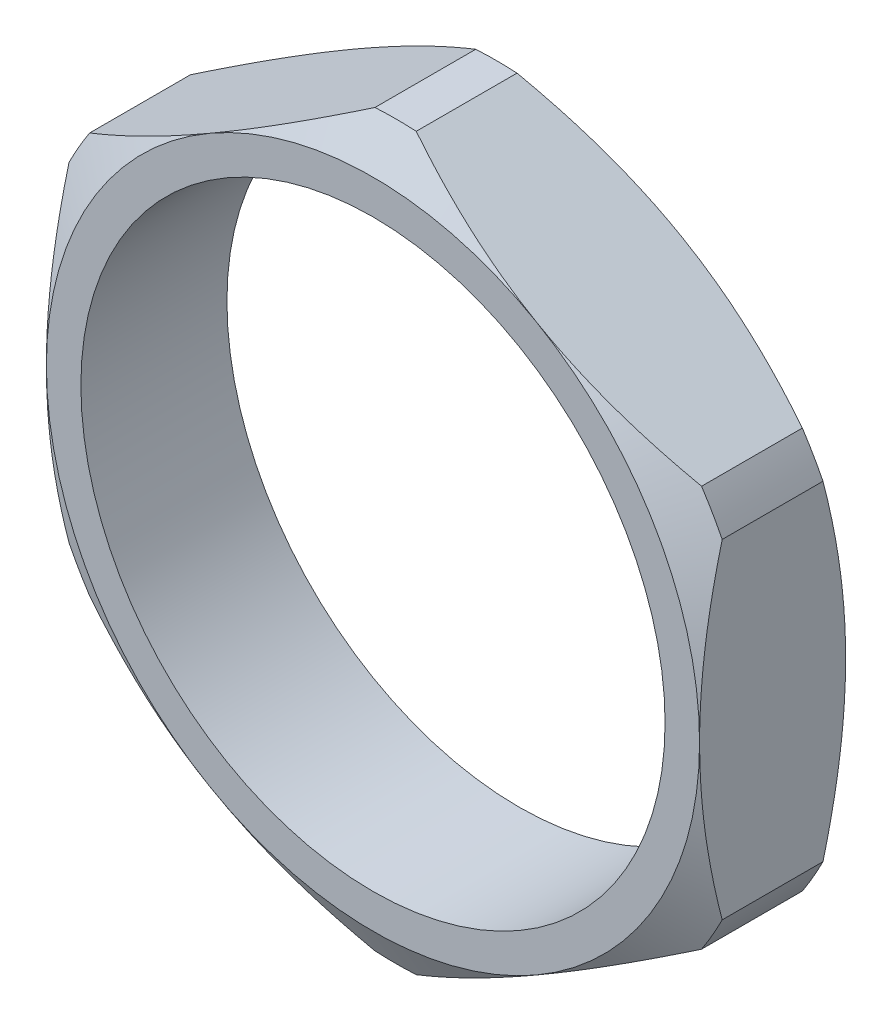
SolidWorks part; units mm, degrees
material "Lead Free Brass, UNS C69300"
ref_plane "Front Plane" through (0, 0, 0) normal (0, 0, 1) x (1, 0, 0)
ref_plane "Top Plane" through (0, 0, 0) normal (0, 1, 0) x (1, 0, 0)
ref_plane "Right Plane" through (0, 0, 0) normal (1, 0, 0) x (0, 0, -1)
sketch "Sketch1" plane through (0, 0, 0) normal (1, 0, 0) x (0, 0, -1)
  line L0 (-1.5875, 0) -> (1.5875, 0) construction
  line L5 (0, 7.1) -> (0, -7.1) construction
  point P5 (0, 6.35)
  point P6 (0, -6.35)
  point P7 (-0.6804, 0)
  dimension "Height" = 3.175
  dimension "Width" = 14.2
  dimension "Thread Size Decimal Equivalent" = 12.7
  dimension "Thread Pitch" = 0.9071
sketch "Sketch2" plane through (0, 0, 0) normal (1, 0, 0) x (0, 0, -1)
  line L0 (-1.5875, 7.1) -> (-1.0956, 7.952)
  line L1 (-1.5875, 7.1) -> (1.5875, 7.1)
  line L2 (-1.5875, 7.1) -> (-1.5875, 6.35)
  line L3 (-1.5875, 6.35) -> (1.5875, 6.35)
  line L4 (1.5875, 7.1) -> (1.5875, 6.35)
  line L5 (-1.0956, 7.952) -> (1.0956, 7.952)
  line L6 (1.0956, 7.952) -> (1.5875, 7.1)
  line L7 (-1.5875, 0) -> (1.5875, 0) construction
  line L8 (-1.5875, 0) -> (1.5875, 0) construction
  line L9 (-2.4379, 6.4482) -> (-1.9844, 5.6626) construction
  line L10 (-1.9844, 5.6626) -> (-1.5308, 6.4482) construction
  line L11 (-1.5308, 6.4482) -> (-2.4379, 6.4482) construction
  line L12 (-2.3812, 6.35) -> (-1.5875, 6.35) construction
  line L13 (-1.9844, 6.4482) -> (-1.9844, 6.35) construction
  line L14 (-1.9844, 6.35) -> (-1.9844, 5.7608) construction
  line L15 (-1.9844, 5.7608) -> (-1.9844, 5.6626) construction
  line L16 (-2.0411, 5.7608) -> (-1.9277, 5.7608)
  line L17 (-2.4096, 6.3991) -> (-1.5592, 6.3991)
  line L18 (-1.9277, 5.7608) -> (-1.5592, 6.3991)
  line L19 (-2.0411, 5.7608) -> (-2.4096, 6.3991)
  point P25 (-1.9844, 6.3991)
  dimension "D1" = 15.904
  dimension "D2" = 60
  dimension "D3" = 0.9071
  dimension "D4" = 0.1134
sketch "Drawing Ref" plane through (0, 0, 0) normal (0, 0, 1) x (1, 0, 0)
  line L0 (0, 0) -> (0, -6.4482) construction
  line L1 (0, 0) -> (4.5596, -4.5596) construction
  circle A0 centre (0, 0) radius 6.4482 construction
  dimension "D1" = 45
sketch "Sketch3" plane through (0, 0, 0) normal (1, 0, 0) x (0, 0, -1)
  line L0 (-1.5875, 7.1) -> (-1.0956, 7.952) construction
  line L1 (-1.0956, 7.952) -> (1.0956, 7.952) construction
  line L2 (1.0956, 7.952) -> (1.5875, 7.1) construction
  line L3 (1.5875, 7.1) -> (1.5875, 6.35) construction
  line L4 (-1.5875, 6.35) -> (1.5875, 6.35) construction
  line L5 (-1.5875, 7.1) -> (-1.5875, 6.35) construction
  line L6 (-1.5875, 7.1) -> (-1.0956, 7.952)
  line L7 (-1.0956, 7.952) -> (1.0956, 7.952)
  line L8 (1.0956, 7.952) -> (1.5875, 7.1)
  line L9 (1.5875, 7.1) -> (1.5875, 6.35)
  line L10 (-1.5875, 6.35) -> (1.5875, 6.35)
  line L11 (-1.5875, 7.1) -> (-1.5875, 6.35)
revolve "Revolve1" add sketch "Sketch3" angle 360 about L0
sketch "Sketch4" plane through (0, 0, 0) normal (0, 0, 1) x (1, 0, 0)
  line L1 (0, 8.1984) -> (-7.1, 4.0992)
  line L2 (-7.1, 4.0992) -> (-7.1, -4.0992)
  line L3 (-7.1, -4.0992) -> (0, -8.1984)
  line L4 (0, -8.1984) -> (7.1, -4.0992)
  line L5 (7.1, -4.0992) -> (7.1, 4.0992)
  line L6 (7.1, 4.0992) -> (0, 8.1984)
  circle A0 centre (0, 0) radius 7.1 construction
extrude "Cut-Extrude1" cut sketch "Sketch4" against normal through all both and the other way through all flip side to cut
sketch "Sketch5" [suppressed] plane through (0, 0, 1.5875) normal (0, 0, 1) x (1, 0, 0)
  circle A0 centre (0, 0) radius 6.35
curve "Helix/Spiral1" [suppressed] pitch 0.9071 height 4.0821 turns 4.5
sketch "Sketch6" [suppressed] plane through (0, 0, 0) normal (1, 0, 0) x (0, 0, -1)
  line L0 (-2.0411, 5.7608) -> (-1.9277, 5.7608) construction
  line L1 (-2.0411, 5.7608) -> (-2.4096, 6.3991) construction
  line L2 (-2.4096, 6.3991) -> (-1.5592, 6.3991) construction
  line L3 (-1.9277, 5.7608) -> (-1.5592, 6.3991) construction
  line L4 (-2.0411, 5.7608) -> (-1.9277, 5.7608)
  line L5 (-2.0411, 5.7608) -> (-2.4096, 6.3991)
  line L6 (-2.4096, 6.3991) -> (-1.5592, 6.3991)
  line L7 (-1.9277, 5.7608) -> (-1.5592, 6.3991)
sweep "Sweep1" [suppressed] add profiles "Sketch6" path "Helix/Spiral1"
sketch "Sketch7" [suppressed] plane through (0, 0, 1.5875) normal (0, 0, 1) x (1, 0, 0)
  circle A0 centre (0, 0) radius 6.4482
extrude "Cut-Extrude3" [suppressed] cut sketch "Sketch7" against normal through all draft 45 and the other way through all
mirror "Mirror1" [suppressed] about plane through (0, 0, 0) normal (0, 0, 1)
sketch "Sketch8" plane through (0, 0, 0) normal (0, 0, 1) x (1, 0, 0)
  circle A0 centre (0, 0) radius 8.1984
equation "\"D1@Sketch2\"=\"Width@Sketch1\" * 1.12"
equation "\"D4@Sketch2\"=\"Thread Pitch@Sketch1\"/8"
equation "\"D3@Sketch2\"=\"Thread Pitch@Sketch1\""
equation "\"D4@Helix/Spiral1\"=\"Thread Pitch@Sketch1\""
equation "\"D3@Helix/Spiral1\"=\"Height@Sketch1\"+\"Thread Pitch@Sketch1\""
